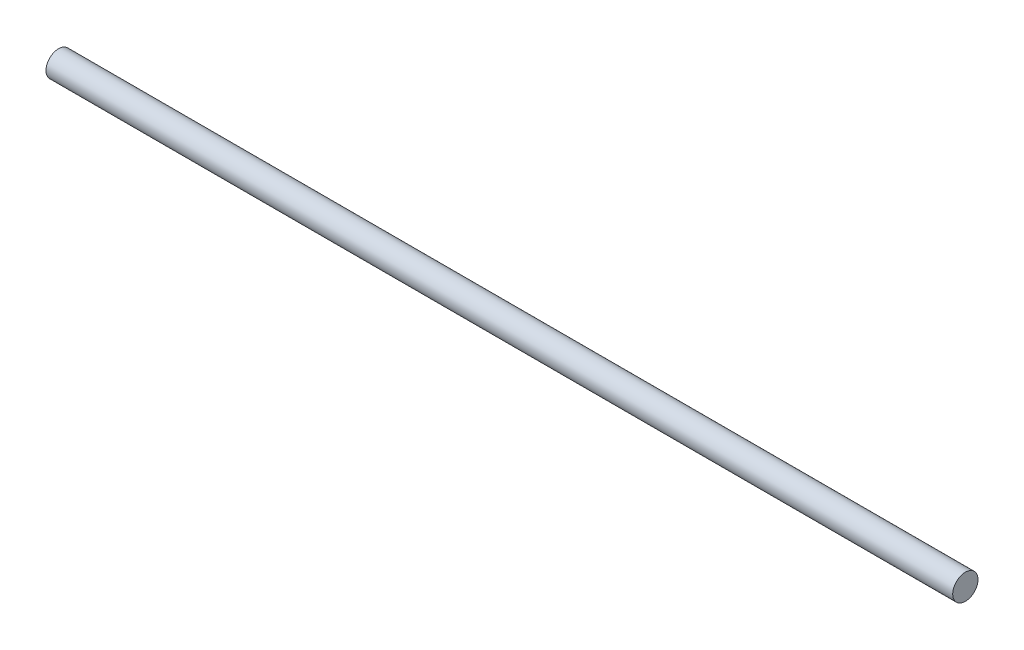
SolidWorks part; units mm, degrees
ref_plane "Front Plane" through (0, 0, 0) normal (0, 0, 1) x (1, 0, 0)
ref_plane "Top Plane" through (0, 0, 0) normal (0, 1, 0) x (1, 0, 0)
ref_plane "Right Plane" through (0, 0, 0) normal (1, 0, 0) x (0, 0, -1)
sketch "Sketch1" plane through (0, 0, 0) normal (1, 0, 0) x (0, 0, -1)
  circle A0 centre (0, 0) radius 0.725
  dimension "D1" = 1.45
extrude "Boss-Extrude1" add sketch "Sketch1" along normal blind 26 and the other way blind 26
